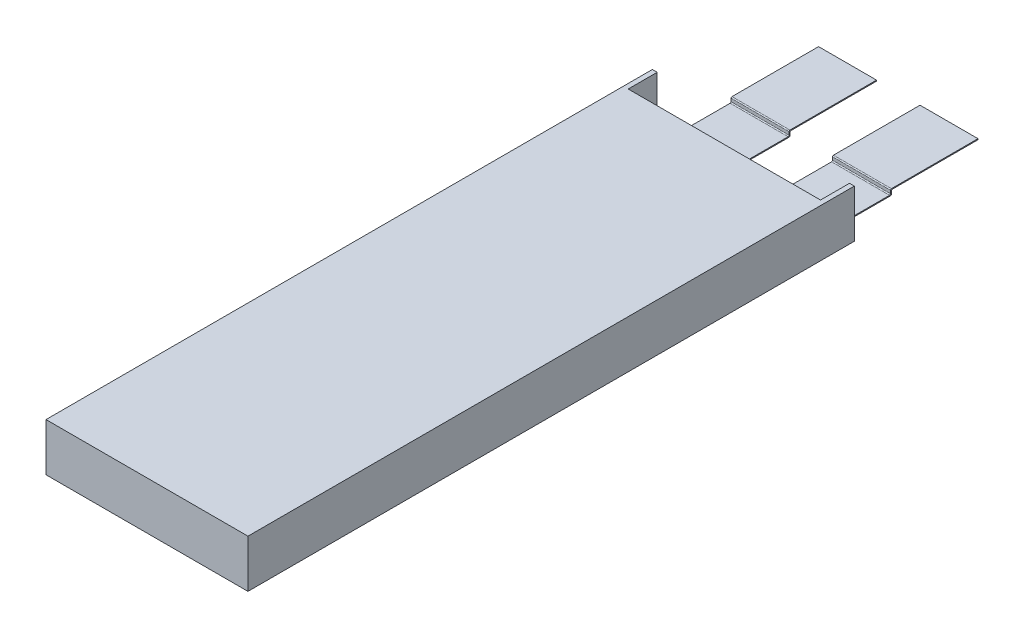
SolidWorks part; units mm, degrees
ref_plane "Front Plane" through (0, 0, 0) normal (0, 0, 1) x (1, 0, 0)
ref_plane "Top Plane" through (0, 0, 0) normal (0, 1, 0) x (1, 0, 0)
ref_plane "Right Plane" through (0, 0, 0) normal (1, 0, 0) x (0, 0, -1)
sketch "Sketch1" plane through (0, 0, 0) normal (0, 1, 0) x (1, 0, 0)
  line L1 (20.9, 62.75) -> (-20.9, 62.75)
  line L2 (20.9, 62.75) -> (20.9, -62.75)
  line L3 (20.9, -62.75) -> (-20.9, -62.75)
  line L4 (-20.9, 62.75) -> (-20.9, -62.75)
  line L5 (20.9, 62.75) -> (-20.9, -62.75) construction
  line L6 (20.9, -62.75) -> (-20.9, 62.75) construction
  point P0 (0, 0)
  dimension "D1" = 41.8
  dimension "D2" = 125.5
extrude "Boss-Extrude1" add sketch "Sketch1" along normal blind 1
sketch "Sketch2" plane through (0, 1, 0) normal (0, 1, 0) x (1, 0, 0)
  line L0 (-20.9, 62.75) -> (-20.9, -62.75) construction
  line L1 (20.9, 56.75) -> (-20.9, 56.75)
  line L2 (20.9, 56.75) -> (20.9, -62.75)
  line L3 (20.9, -62.75) -> (-20.9, -62.75)
  line L4 (-20.9, 56.75) -> (-20.9, -62.75)
  line L5 (20.9, 56.75) -> (-20.9, -62.75) construction
  line L6 (20.9, -62.75) -> (-20.9, 56.75) construction
  line L7 (20.9, 62.75) -> (-20.9, 62.75) construction
  line L8 (-20.9, -62.75) -> (20.9, -62.75) construction
  line L10 (20.9, -62.75) -> (20.9, 62.75) construction
  point P0 (0, -3)
  dimension "D1" = 6
extrude "Boss-Extrude2" add sketch "Sketch2" along normal blind 8.9
sketch "Sketch3" plane through (0, 1, 0) normal (0, 1, 0) x (1, 0, 0)
  line L0 (20.9, 56.75) -> (-20.9, 56.75) construction
  line L1 (-20.9, 62.75) -> (-19.9, 62.75)
  line L2 (-20.9, 62.75) -> (-20.9, 56.75)
  line L3 (-20.9, 56.75) -> (-19.9, 56.75)
  line L4 (-19.9, 62.75) -> (-19.9, 56.75)
  line L5 (0, 56.75) -> (0, 62.75) construction
  line L6 (20.9, 56.75) -> (-20.9, 56.75) construction
  line L7 (20.9, 62.75) -> (-20.9, 62.75) construction
  dimension "D1" = 1
extrude "Boss-Extrude3" add sketch "Sketch3" along normal blind 8.9
sketch "Sketch4" plane through (0, 0, 0) normal (1, 0, 0) x (0, 0, -1)
  line L0 (74.8376, 1.2) -> (92.75, 1.2)
  line L2 (92.75, 1.2) -> (92.75, 1)
  line L3 (92.75, 1) -> (75.0376, 1)
  line L4 (62.75, 0) -> (74.6376, 0)
  line L5 (62.75, 0) -> (62.75, 0.2)
  line L6 (62.75, 1) -> (62.75, 0) construction
  line L7 (62.75, 0.2) -> (74.4376, 0.2)
  line L8 (74.6376, 1) -> (74.6376, 0.4)
  line L9 (74.8376, 0.8) -> (74.8376, 0.2)
  arc A0 (74.8376, 1.2) -> (74.6376, 1) centre (74.8376, 1) ccw
  arc A1 (74.4376, 0.2) -> (74.6376, 0.4) centre (74.4376, 0.4) ccw
  arc A2 (74.6376, 0) -> (74.8376, 0.2) centre (74.6376, 0.2) ccw
  arc A3 (75.0376, 1) -> (74.8376, 0.8) centre (75.0376, 0.8) ccw
  dimension "D6" = 0.2
  dimension "D1" = 0.2
  dimension "D2" = 0.2
  dimension "D3" = 1
  dimension "D4" = 30
  dimension "D5" = 0.2
extrude "Boss-Extrude4" add sketch "Sketch4" along normal blind 12 from offset 4.5
mirror "Mirror1" about plane through (0, 0, 0) normal (1, 0, 0) of "Boss-Extrude4", "Boss-Extrude3"
